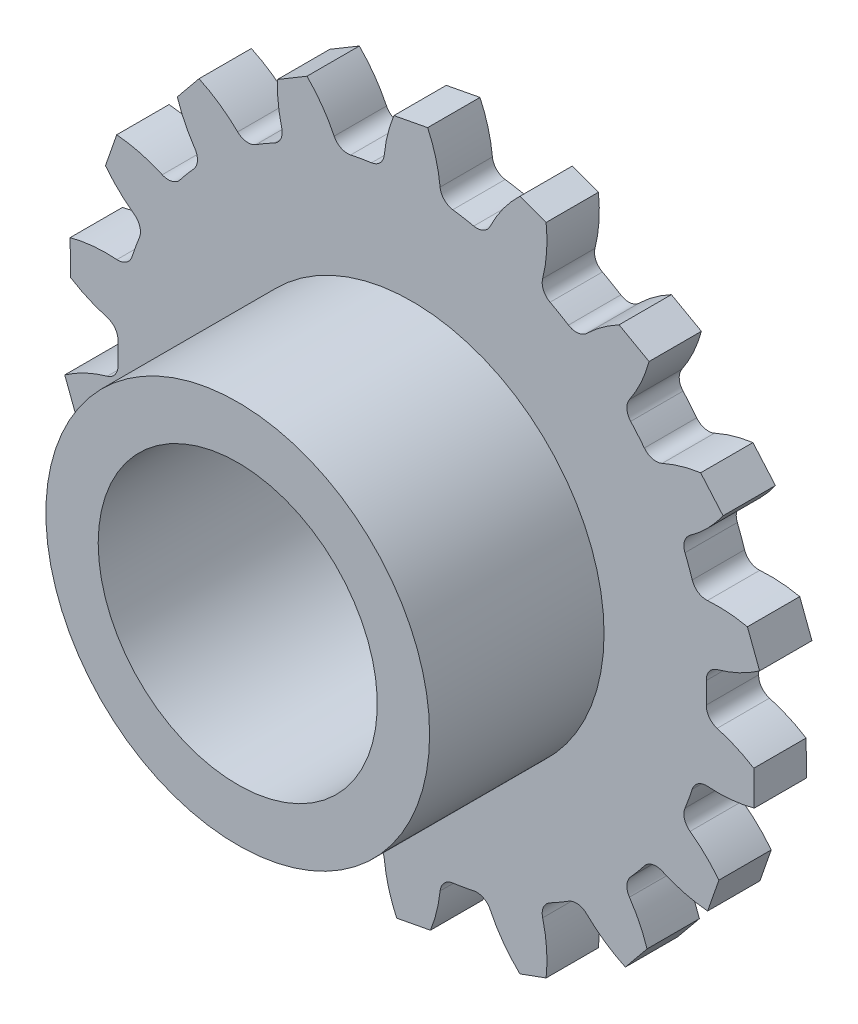
SolidWorks part; units mm, degrees
ref_plane "前视基准面" through (0, 0, 0) normal (0, 0, 1) x (1, 0, 0)
ref_plane "上视基准面" through (0, 0, 0) normal (0, 1, 0) x (1, 0, 0)
ref_plane "右视基准面" through (0, 0, 0) normal (1, 0, 0) x (0, 0, -1)
ref_plane "基准面1" through (0, 0, 3) normal (0, 0, 1) x (1, 0, 0)
sketch "草图1" plane through (0, 0, 3) normal (0, 0, 1) x (1, 0, 0)
  line L0 (7.6776, 18.755) -> (6.1741, 19.3023)
  line L1 (6.1741, -19.3023) -> (7.6776, -18.755)
  arc A0 (16.2552, 4.5314) -> (15.3649, 6.9774) centre (0, 0) ccw
  arc A1 (15.3649, 6.9774) -> (18.6559, 10.771) centre (11.2076, 13.9082) ccw
  arc A2 (18.6559, 10.771) -> (13.7251, 9.8177) centre (17.6486, 2.752) ccw
  arc A3 (13.7251, 9.8177) -> (12.0519, 11.8118) centre (0, 0) ccw
  arc A4 (12.0519, 11.8118) -> (13.8469, 16.5021) centre (5.7749, 16.9026) ccw
  arc A5 (13.8469, 16.5021) -> (9.5395, 13.9199) centre (15.6431, 8.6222) ccw
  arc A6 (9.5395, 13.9199) -> (7.2852, 15.2214) centre (0, 0) ccw
  arc A7 (7.2852, 15.2214) -> (7.6776, 18.755) centre (-0.3545, 17.8584) ccw
  arc A8 (6.1741, 19.3023) -> (4.2033, 16.3431) centre (11.7507, 13.4525) ccw
  arc A9 (4.2033, 16.3431) -> (1.6398, 16.7951) centre (0, 0) ccw
  arc A10 (1.6398, 16.7951) -> (0, 21.5419) centre (-6.441, 16.6602) ccw
  arc A11 (0, 21.5419) -> (-1.6398, 16.7951) centre (6.441, 16.6602) ccw
  arc A12 (-1.6398, 16.7951) -> (-4.2033, 16.3431) centre (0, 0) ccw
  arc A13 (-4.2033, 16.3431) -> (-7.3678, 20.2428) centre (-11.7507, 13.4525) ccw
  arc A14 (-7.3678, 20.2428) -> (-7.2852, 15.2214) centre (0.3545, 17.8584) ccw
  arc A15 (-7.2852, 15.2214) -> (-9.5395, 13.9199) centre (0, 0) ccw
  arc A16 (-9.5395, 13.9199) -> (-13.8469, 16.5021) centre (-15.6431, 8.6222) ccw
  arc A17 (-13.8469, 16.5021) -> (-12.0519, 11.8118) centre (-5.7749, 16.9026) ccw
  arc A18 (-12.0519, 11.8118) -> (-13.7251, 9.8177) centre (0, 0) ccw
  arc A19 (-13.7251, 9.8177) -> (-18.6559, 10.771) centre (-17.6486, 2.752) ccw
  arc A20 (-18.6559, 10.771) -> (-15.3649, 6.9774) centre (-11.2076, 13.9082) ccw
  arc A21 (-15.3649, 6.9774) -> (-16.2552, 4.5314) centre (0, 0) ccw
  arc A22 (-16.2552, 4.5314) -> (-21.2147, 3.7407) centre (-17.5255, -3.4501) ccw
  arc A23 (-21.2147, 3.7407) -> (-16.8247, 1.3015) centre (-15.2886, 9.2362) ccw
  arc A24 (-16.8247, 1.3015) -> (-16.8247, -1.3015) centre (0, 0) ccw
  arc A25 (-16.8247, -1.3015) -> (-21.2147, -3.7407) centre (-15.2886, -9.2362) ccw
  arc A26 (-21.2147, -3.7407) -> (-16.2552, -4.5314) centre (-17.5255, 3.4501) ccw
  arc A27 (-16.2552, -4.5314) -> (-15.3649, -6.9774) centre (0, 0) ccw
  arc A28 (-15.3649, -6.9774) -> (-18.6559, -10.771) centre (-11.2076, -13.9082) ccw
  arc A29 (-18.6559, -10.771) -> (-13.7251, -9.8177) centre (-17.6486, -2.752) ccw
  arc A30 (-13.7251, -9.8177) -> (-12.0519, -11.8118) centre (0, 0) ccw
  arc A31 (-12.0519, -11.8118) -> (-13.8469, -16.5021) centre (-5.7749, -16.9026) ccw
  arc A32 (-13.8469, -16.5021) -> (-9.5395, -13.9199) centre (-15.6431, -8.6222) ccw
  arc A33 (-9.5395, -13.9199) -> (-7.2852, -15.2214) centre (0, 0) ccw
  arc A34 (-7.2852, -15.2214) -> (-7.3678, -20.2428) centre (0.3545, -17.8584) ccw
  arc A35 (-7.3678, -20.2428) -> (-4.2033, -16.3431) centre (-11.7507, -13.4525) ccw
  arc A36 (-4.2033, -16.3431) -> (-1.6398, -16.7951) centre (0, 0) ccw
  arc A37 (-1.6398, -16.7951) -> (0, -21.5419) centre (6.441, -16.6602) ccw
  arc A38 (0, -21.5419) -> (1.6398, -16.7951) centre (-6.441, -16.6602) ccw
  arc A39 (1.6398, -16.7951) -> (4.2033, -16.3431) centre (0, 0) ccw
  arc A40 (4.2033, -16.3431) -> (6.1741, -19.3023) centre (11.7507, -13.4525) ccw
  arc A41 (7.6776, -18.755) -> (7.2852, -15.2214) centre (-0.3545, -17.8584) ccw
  arc A42 (7.2852, -15.2214) -> (9.5395, -13.9199) centre (0, 0) ccw
  arc A43 (9.5395, -13.9199) -> (13.8469, -16.5021) centre (15.6431, -8.6222) ccw
  arc A44 (13.8469, -16.5021) -> (12.0519, -11.8118) centre (5.7749, -16.9026) ccw
  arc A45 (12.0519, -11.8118) -> (13.7251, -9.8177) centre (0, 0) ccw
  arc A46 (13.7251, -9.8177) -> (18.6559, -10.771) centre (17.6486, -2.752) ccw
  arc A47 (18.6559, -10.771) -> (15.3649, -6.9774) centre (11.2076, -13.9082) ccw
  arc A48 (15.3649, -6.9774) -> (16.2552, -4.5314) centre (0, 0) ccw
  arc A49 (16.2552, -4.5314) -> (21.2147, -3.7407) centre (17.5255, 3.4501) ccw
  arc A50 (21.2147, -3.7407) -> (16.8247, -1.3015) centre (15.2886, -9.2362) ccw
  arc A51 (16.8247, -1.3015) -> (16.8247, 1.3015) centre (0, 0) ccw
  arc A52 (16.8247, 1.3015) -> (21.2147, 3.7407) centre (15.2886, 9.2362) ccw
  arc A53 (21.2147, 3.7407) -> (16.2552, 4.5314) centre (17.5255, -3.4501) ccw
extrude "凸台-拉伸1" add sketch "草图1" against normal blind 3
sketch "草图2" plane through (0, 0, 0) normal (0, 1, 0) x (1, 0, 0)
  line L0 (11, -3) -> (0, -3)
  line L1 (0, -3) -> (0, -13)
  line L2 (0, -13) -> (11, -13)
  line L3 (11, -13) -> (11, -3)
  line L4 (0, -3) -> (0, -13) construction
revolve "旋转1" add sketch "草图2" angle 360 about L4 reverse direction yes
hole_wizard "Ø16.0 (16) 直径孔1" positions "草图4" profile "草图3" hole size "Ø16.0" standard "ANSI Metric"
sketch "草图4" plane through (0, 0, 0) normal (0, 0, -1) x (-1, 0, 0)
  point P0 (0, 0)
sketch "草图3" plane through (0, 0, 0) normal (1, 0, 0) x (0, 1, 0)
  line L0 (0, 0) -> (0, 13)
  line L1 (0, 13) -> (8, 13)
  line L2 (8, 13) -> (8, 0)
  line L5 (8, 0) -> (0, 0)
  line L11 (0, -6.35) -> (0, 107.95) construction
  dimension "通孔孔直径" = 16
  dimension "通孔孔深度" = 13
chamfer "倒角1" distance 1.8012 angle 63.63 16 edges at (-13.8469, 16.5021, 1.5) (21.2147, 3.7407, 1.5) (18.6559, -10.771, 1.5) (-21.2147, 3.7407, 1.5) (0, 21.5419, 1.5) (-21.2147, -3.7407, 1.5) (13.8469, -16.5021, 1.5) (-18.6559, -10.771, 1.5) (21.2147, -3.7407, 1.5) (-13.8469, -16.5021, 1.5) (13.8469, 16.5021, 1.5) (18.6559, 10.771, 1.5) (-7.3678, 20.2428, 1.5) (-7.3678, -20.2428, 1.5) (-18.6559, 10.771, 1.5) (0, -21.5419, 1.5) first distance on face at (-11.5904, 15.3825, 1.5) first distance on face at (19.1168, 2.3463, 1.5) first distance on face at (16.1525, -10.4907, 1.5) first distance on face at (-18.7664, 4.3335, 1.5) first distance on face at (1.0089, 19.2338, 1.5) first distance on face at (-19.1168, -2.3463, 1.5) first distance on face at (11.5904, -15.3825, 1.5) first distance on face at (-17.1615, -8.7432, 1.5) first distance on face at (18.7664, -4.3335, 1.5) first distance on face at (-13.1362, -14.0854, 1.5) first distance on face at (13.1362, 14.0854, 1.5) first distance on face at (17.1615, 8.7432, 1.5) first distance on face at (-5.6303, 18.419, 1.5) first distance on face at (-7.5265, -17.7288, 1.5) first distance on face at (-16.1525, 10.4907, 1.5) first distance on face at (-1.0089, -19.2338, 1.5)
fillet "圆角1" radius 0.85 36 edges at (16.2552, -4.5314, 1.5) (-1.6398, -16.7951, 1.5) (-12.0519, -11.8118, 1.5) (13.7251, 9.8177, 1.5) (9.5395, -13.9199, 1.5) (12.0519, 11.8118, 1.5) (15.3649, 6.9774, 1.5) (9.5395, 13.9199, 1.5) (-7.2852, -15.2214, 1.5) (7.2852, 15.2214, 1.5) (4.2033, -16.3431, 1.5) (4.2033, 16.3431, 1.5) (13.7251, -9.8177, 1.5) (1.6398, 16.7951, 1.5) (16.8247, 1.3015, 1.5) (-1.6398, 16.7951, 1.5) (-13.7251, -9.8177, 1.5) (-4.2033, 16.3431, 1.5) (-9.5395, -13.9199, 1.5) (-7.2852, 15.2214, 1.5) (-4.2033, -16.3431, 1.5) (-12.0519, 11.8118, 1.5) (1.6398, -16.7951, 1.5) (-13.7251, 9.8177, 1.5) (7.2852, -15.2214, 1.5) (-15.3649, 6.9774, 1.5) (12.0519, -11.8118, 1.5) (-16.2552, 4.5314, 1.5) (15.3649, -6.9774, 1.5) (-16.8247, 1.3015, 1.5) (16.8247, -1.3015, 1.5) (-16.8247, -1.3015, 1.5) (16.2552, 4.5314, 1.5) (-16.2552, -4.5314, 1.5) (-15.3649, -6.9774, 1.5) (-9.5395, 13.9199, 1.5) tangent propagation no
